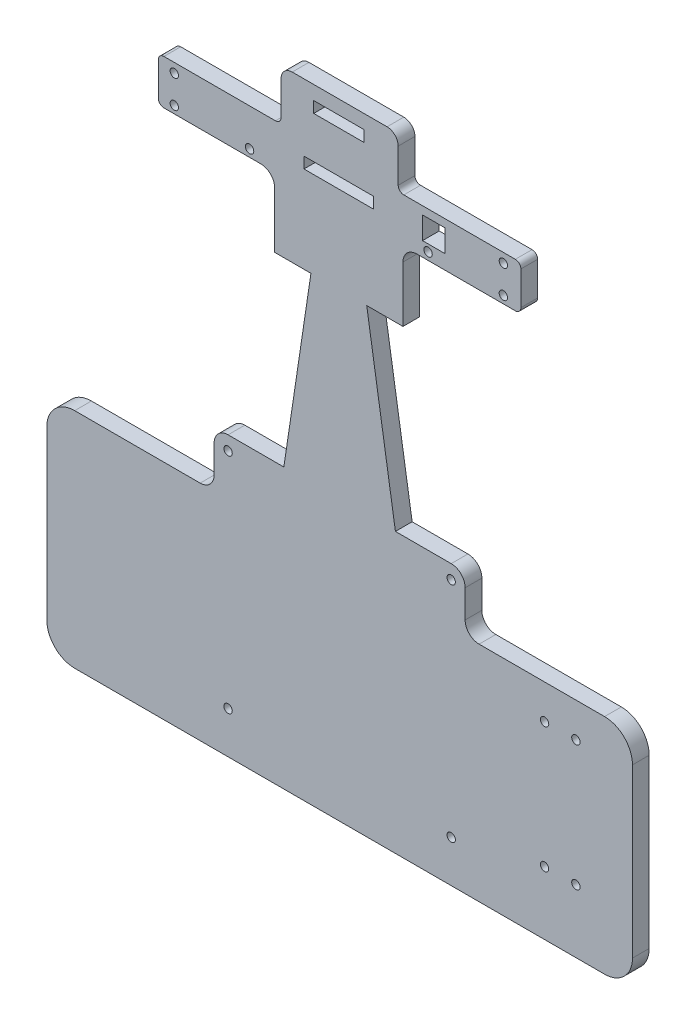
SolidWorks part; units mm, degrees
ref_plane "Front Plane" through (0, 0, 0) normal (0, 0, 1) x (1, 0, 0)
ref_plane "Top Plane" through (0, 0, 0) normal (0, 1, 0) x (1, 0, 0)
ref_plane "Right Plane" through (0, 0, 0) normal (1, 0, 0) x (0, 0, -1)
sketch "Sketch1" plane through (0, 0, 0) normal (0, 0, 1) x (1, 0, 0)
  line L0 (-36.0728, -10.1516) -> (153.9272, -10.1516)
  line L1 (-46.0728, -0.1516) -> (-46.0728, 59.8484)
  line L2 (163.9272, -0.1516) -> (163.9272, 59.8484)
  line L3 (153.9272, 69.8484) -> (108.9272, 69.8484)
  line L4 (-36.0728, 69.8484) -> (8.9272, 69.8484)
  line L5 (13.9272, 74.8484) -> (13.9272, 84.8484)
  line L6 (103.9272, 74.8484) -> (103.9272, 84.8484)
  line L12 (-4.0728, 179.8484) -> (30.6382, 179.8484)
  line L13 (86.6382, 179.8484) -> (121.9272, 179.8484)
  line L14 (-6.0728, 181.8484) -> (-6.0728, 193.8484)
  line L15 (123.9272, 181.8484) -> (123.9272, 193.8484)
  line L17 (121.9272, 195.8484) -> (81.9272, 195.8484)
  line L18 (-4.0728, 195.8484) -> (35.9272, 195.8484)
  line L19 (96.6382, 185) -> (88.6382, 185)
  line L20 (46.1382, 186) -> (71.1382, 186)
  line L21 (71.1382, 186) -> (71.1382, 190)
  line L22 (46.1382, 186) -> (46.1382, 190)
  line L23 (46.1382, 190) -> (71.1382, 190)
  line L24 (96.6382, 185) -> (96.6382, 193)
  line L25 (96.6382, 193) -> (88.6382, 193)
  line L26 (88.6382, 193) -> (88.6382, 185)
  line L27 (58.6382, -791) -> (58.6382, 49209) construction
  line L29 (49.6382, 209) -> (67.6382, 209)
  line L33 (67.6382, 209) -> (67.6382, 205)
  line L34 (49.6382, 209) -> (49.6382, 205)
  line L35 (49.6382, 205) -> (67.6382, 205)
  line L38 (79.9272, 197.8484) -> (79.9272, 210)
  line L40 (37.9272, 197.8484) -> (37.9272, 210)
  line L43 (41.9272, 214) -> (75.9272, 214)
  line L44 (81.6382, 154.8484) -> (81.6382, 174.8484)
  line L45 (-963.3618, 167.3484) -> (49036.6382, 167.3484) construction
  line L46 (35.6382, 154.8484) -> (35.6382, 174.8484)
  line L47 (81.6382, 154.8484) -> (68.6382, 154.8484)
  line L48 (35.6382, 154.8484) -> (48.6382, 154.8484)
  line L49 (98.9272, 89.8484) -> (78.9272, 89.8484)
  line L50 (18.9272, 89.8484) -> (38.9272, 89.8484)
  line L51 (-1046.0728, 29.8484) -> (48953.9272, 29.8484) construction
  line L52 (78.9272, 89.8484) -> (68.6382, 154.8484)
  line L53 (38.9272, 89.8484) -> (48.6382, 154.8484)
  circle A0 centre (143.6382, 57.5) radius 1.5
  circle A1 centre (132.4138, 57.5) radius 1.5
  circle A2 centre (132.4138, 12.5) radius 1.5
  circle A3 centre (143.6382, 12.5) radius 1.5
  arc A8 (163.9272, 59.8484) -> (153.9272, 69.8484) centre (153.9272, 59.8484) ccw
  arc A9 (163.9272, -0.1516) -> (153.9272, -10.1516) centre (153.9272, -0.1516) cw
  arc A10 (-36.0728, -10.1516) -> (-46.0728, -0.1516) centre (-36.0728, -0.1516) cw
  arc A11 (-36.0728, 69.8484) -> (-46.0728, 59.8484) centre (-36.0728, 59.8484) ccw
  arc A12 (103.9272, 84.8484) -> (98.9272, 89.8484) centre (98.9272, 84.8484) ccw
  arc A13 (18.9272, 89.8484) -> (13.9272, 84.8484) centre (18.9272, 84.8484) ccw
  arc A14 (8.9272, 69.8484) -> (13.9272, 74.8484) centre (8.9272, 74.8484) ccw
  arc A15 (108.9272, 69.8484) -> (103.9272, 74.8484) centre (108.9272, 74.8484) cw
  circle A21 centre (117.6382, 182.5) radius 1.5
  circle A22 centre (117.6382, 192.5) radius 1.5
  circle A23 centre (-0.3618, 182.5) radius 1.5
  circle A24 centre (-0.3618, 192.5) radius 1.5
  circle A30 centre (26.6382, 182.5) radius 1.5
  circle A31 centre (90.6382, 182.5) radius 1.5
  arc A32 (81.9272, 195.8484) -> (79.9272, 197.8484) centre (81.9272, 197.8484) cw
  arc A33 (35.9272, 195.8484) -> (37.9272, 197.8484) centre (35.9272, 197.8484) ccw
  arc A34 (-4.0728, 179.8484) -> (-6.0728, 181.8484) centre (-4.0728, 181.8484) cw
  arc A35 (-6.0728, 193.8484) -> (-4.0728, 195.8484) centre (-4.0728, 193.8484) cw
  arc A36 (123.9272, 181.8484) -> (121.9272, 179.8484) centre (121.9272, 181.8484) cw
  arc A37 (123.9272, 193.8484) -> (121.9272, 195.8484) centre (121.9272, 193.8484) ccw
  circle A40 centre (98.9272, 84.8484) radius 1.5
  circle A41 centre (18.9272, 84.8484) radius 1.5
  circle A42 centre (98.9272, 4.8484) radius 1.5
  circle A43 centre (18.9272, 4.8484) radius 1.5
  arc A44 (75.9272, 214) -> (79.9272, 210) centre (75.9272, 210) cw
  arc A45 (41.9272, 214) -> (37.9272, 210) centre (41.9272, 210) ccw
  circle A46 centre (39.6382, 167.3484) radius 1.5
  circle A47 centre (77.6382, 167.3484) radius 1.5
  arc A48 (86.6382, 179.8484) -> (81.6382, 174.8484) centre (86.6382, 174.8484) ccw
  arc A49 (30.6382, 179.8484) -> (35.6382, 174.8484) centre (30.6382, 174.8484) cw
  point P78 (58.6382, 214)
  point P87 (58.6382, 209)
  point P89 (58.6382, 214)
  point P90 (58.6382, 214)
  point P92 (58.6382, 214)
  point P119 (58.6382, 154.8484)
  point P123 (-46.0728, 29.8484)
  dimension "D1" = 4
  dimension "D2" = 5
  dimension "D3" = 80
extrude "Boss-Extrude3" add sketch "Sketch1" against normal blind 6 contours L40 A45 L43 A44 L38 A32 L17 A37 L15 A36 L13 A48 L44 L47 L52 L49 A12 L6 A15 L3 A8 L2 A9 L0 A10 L1 A11 L4 A14 L5 A13 L50 L53 L48 L46 A49 L12 A34 L14 A35 L18 A33 | L24 L25 L26 L19 | L21 L20 L22 L23 | L35 L33 L29 L34 | A30 | A23 | A24 | A22 | A21 | A31 | A3 | A2 | A1 | A0
extrude "Cut-Extrude1" cut sketch "Sketch1<8>" against normal blind 6 rebuild error yes
sketch "Sketch1<8>" plane through (0, 0, 0) normal (0, 0, 1) x (1, 0, 0) same geometry as "Sketch1"
extrude "Cut-Extrude2" cut sketch "Sketch1<9>" against normal blind 6 contours A40 | A42 | A43 | A41
sketch "Sketch1<9>" plane through (0, 0, 0) normal (0, 0, 1) x (1, 0, 0) same geometry as "Sketch1"
